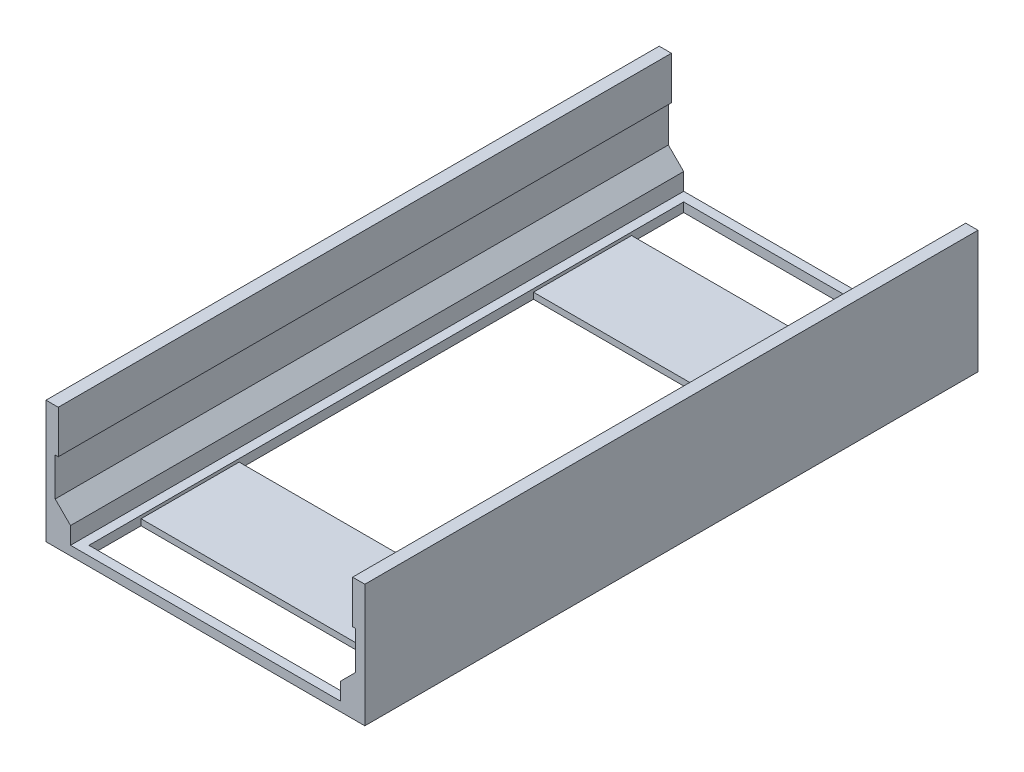
SolidWorks part; units mm, degrees
ref_plane "Plano frontal" through (0, 0, 0) normal (0, 0, 1) x (1, 0, 0)
ref_plane "Plano superior" through (0, 0, 0) normal (0, 1, 0) x (1, 0, 0)
ref_plane "Plano direito" through (0, 0, 0) normal (1, 0, 0) x (0, 0, -1)
sketch "Esboço1" plane through (0, 0, 0) normal (0, 0, 1) x (1, 0, 0)
  line L0 (-24, 14) -> (-24, -14) construction
  line L1 (24, 14) -> (24, -14) construction
  line L2 (-22.5, 12.5) -> (-22.5, -7.5)
  line L3 (-17.5, -12.5) -> (17.5, -12.5)
  line L4 (22.5, 12.5) -> (22.5, -7.5)
  line L5 (-22.5, 12.5) -> (22.5, -12.5) construction
  line L6 (-22.5, -12.5) -> (22.5, 12.5) construction
  line L7 (24, 12.5) -> (24, -9)
  line L8 (-19, -14) -> (19, -14)
  line L9 (-24, 12.5) -> (-24, -9)
  line L10 (-22.5, 12.5) -> (-24, 12.5)
  line L11 (22.5, 12.5) -> (24, 12.5)
  line L12 (-22.5, -12.5) -> (22.5, -12.5) construction
  line L13 (-22.5, 12.5) -> (22.5, 12.5) construction
  line L14 (-24, 14) -> (24, 14) construction
  line L15 (22.5, 12.5) -> (22.5, -12.5) construction
  line L16 (17.5, -12.5) -> (22.5, -7.5)
  line L17 (-24, -14) -> (24, -14) construction
  line L18 (24, -9) -> (19, -14)
  line L19 (-22.5, 12.5) -> (-22.5, -12.5) construction
  line L20 (-22.5, -7.5) -> (-17.5, -12.5)
  line L21 (-24, -9) -> (-19, -14)
  point P0 (0, 0)
  dimension "D1" = 25
  dimension "D2" = 45
  dimension "D3" = 1.5
extrude "Ressalto-extrusão1" add sketch "Esboço1" along normal blind 100
sketch "Esboço3" plane through (0, -12.5, 0) normal (0, 1, 0) x (1, 0, 0)
  line L0 (22.5, -100) -> (22.5, 0) construction
  line L1 (-22.5, 0) -> (22.5, 0)
  line L2 (-22.5, 0) -> (-22.5, -1.5)
  line L3 (-22.5, -1.5) -> (22.5, -1.5)
  line L4 (22.5, 0) -> (22.5, -1.5)
  dimension "D1" = 1.5
extrude "Ressalto-extrusão3" add sketch "Esboço3" along normal up to surface (25 mm away) up to face at (-23.25, 12.5, 50)
sketch "Esboço4" plane through (0, 0, 1.5) normal (0, 0, 1) x (1, 0, 0)
  line L0 (17.5, -12.5) -> (-17.5, -12.5) construction
  line L1 (-10, -12.5) -> (10, -12.5)
  line L2 (-10, -12.5) -> (-10, -7.5)
  line L3 (-5, -2.5) -> (5, -2.5)
  line L4 (10, -12.5) -> (10, -7.5)
  line L5 (-10, -7.5) -> (-5, -2.5)
  line L6 (5, -2.5) -> (10, -7.5)
  point P1 (10, -2.5)
  point P2 (-10, -2.5)
  point P4 (0, -12.5)
  point P5 (0, -12.5)
extrude "Corte-extrusão1" cut sketch "Esboço4" against normal through all
sketch "Esboço5" plane through (0, -12.5, 0) normal (0, 1, 0) x (1, 0, 0)
  line L0 (0, 0) -> (0, -2.25) construction
  line L1 (22.5, -1.5) -> (-22.5, -1.5) construction
  line L2 (-6, -3) -> (6, -3)
  line L3 (-6, -3) -> (-6, -1.5)
  line L4 (-6, -1.5) -> (6, -1.5)
  line L5 (6, -3) -> (6, -1.5)
  line L6 (-6, -3) -> (6, -1.5) construction
  line L7 (-6, -1.5) -> (6, -3) construction
  dimension "D1" = 2.25
  dimension "D2" = 12
extrude "Corte-extrusão2" cut sketch "Esboço5" against normal through all
sketch "Esboço6" plane through (0, -12.5, 0) normal (0, 1, 0) x (1, 0, 0)
  line L0 (22.5, -100) -> (22.5, -1.5) construction
  line L1 (-22.5, -100) -> (22.5, -100)
  line L2 (-22.5, -100) -> (-22.5, -98)
  line L3 (-22.5, -98) -> (22.5, -98)
  line L4 (22.5, -100) -> (22.5, -98)
extrude "Ressalto-extrusão4" add sketch "Esboço6" along normal up to surface (25 mm away) up to face at (0, 12.5, 50.375)
sketch "Esboço7" plane through (0, 0, 100) normal (0, 0, 1) x (1, 0, 0)
  line L0 (0, 12.5) -> (0, 8.5) construction
  line L1 (24, 12.5) -> (-24, 12.5) construction
  line L2 (0, 8.5) -> (1, 8.5) construction
  line L3 (1, 8.5) -> (0, 8.5) construction
  line L4 (0, 8.5) -> (0, 0.5) construction
  line L5 (0, 0.5) -> (1, 0.5) construction
  line L6 (1, 0.5) -> (0, 0.5) construction
  line L7 (0, 0.5) -> (0, -7.5) construction
  line L8 (0, 8.5) -> (-8, 8.5) construction
  line L9 (-8, 8.5) -> (-16, 8.5) construction
  line L10 (-9.4, 9.9) -> (-6.6, 9.9)
  line L11 (-17.4, 9.9) -> (-14.6, 9.9)
  line L12 (-17.4, 9.9) -> (-17.4, 7.1)
  line L13 (-17.4, 7.1) -> (-14.6, 7.1)
  line L14 (-14.6, 9.9) -> (-14.6, 7.1)
  line L15 (-17.4, 9.9) -> (-14.6, 7.1) construction
  line L16 (-17.4, 7.1) -> (-14.6, 9.9) construction
  line L17 (-9.4, 9.9) -> (-9.4, 7.1)
  line L18 (-9.4, 7.1) -> (-6.6, 7.1)
  line L19 (-6.6, 9.9) -> (-6.6, 7.1)
  line L20 (-9.4, 9.9) -> (-6.6, 7.1) construction
  line L21 (-9.4, 7.1) -> (-6.6, 9.9) construction
  line L22 (-1.4, 9.9) -> (1.4, 9.9)
  line L23 (-1.4, 9.9) -> (-1.4, 7.1)
  line L24 (-1.4, 7.1) -> (1.4, 7.1)
  line L25 (1.4, 9.9) -> (1.4, 7.1)
  line L26 (-1.4, 9.9) -> (1.4, 7.1) construction
  line L27 (-1.4, 7.1) -> (1.4, 9.9) construction
  line L28 (6.6, 9.9) -> (9.4, 9.9)
  line L29 (6.6, 9.9) -> (6.6, 7.1)
  line L30 (6.6, 7.1) -> (9.4, 7.1)
  line L31 (9.4, 9.9) -> (9.4, 7.1)
  line L32 (6.6, 9.9) -> (9.4, 7.1) construction
  line L33 (6.6, 7.1) -> (9.4, 9.9) construction
  line L34 (14.6, 9.9) -> (17.4, 9.9)
  line L35 (14.6, 9.9) -> (14.6, 7.1)
  line L36 (14.6, 7.1) -> (17.4, 7.1)
  line L37 (17.4, 9.9) -> (17.4, 7.1)
  line L38 (14.6, 9.9) -> (17.4, 7.1) construction
  line L39 (14.6, 7.1) -> (17.4, 9.9) construction
  line L40 (-9.4, 1.9) -> (-6.6, 1.9)
  line L41 (-9.4, 1.9) -> (-9.4, -0.9)
  line L42 (-9.4, -0.9) -> (-6.6, -0.9)
  line L43 (-6.6, 1.9) -> (-6.6, -0.9)
  line L44 (-9.4, 1.9) -> (-6.6, -0.9) construction
  line L45 (-9.4, -0.9) -> (-6.6, 1.9) construction
  line L46 (-1.4, 1.9) -> (1.4, 1.9)
  line L47 (-1.4, 1.9) -> (-1.4, -0.9)
  line L48 (-1.4, -0.9) -> (1.4, -0.9)
  line L49 (1.4, 1.9) -> (1.4, -0.9)
  line L50 (-1.4, 1.9) -> (1.4, -0.9) construction
  line L51 (-1.4, -0.9) -> (1.4, 1.9) construction
  line L52 (6.6, 1.9) -> (9.4, 1.9)
  line L53 (6.6, 1.9) -> (6.6, -0.9)
  line L54 (6.6, -0.9) -> (9.4, -0.9)
  line L55 (9.4, 1.9) -> (9.4, -0.9)
  line L56 (6.6, 1.9) -> (9.4, -0.9) construction
  line L57 (6.6, -0.9) -> (9.4, 1.9) construction
  line L58 (14.6, 1.9) -> (17.4, 1.9)
  line L59 (14.6, 1.9) -> (14.6, -0.9)
  line L60 (14.6, -0.9) -> (17.4, -0.9)
  line L61 (17.4, 1.9) -> (17.4, -0.9)
  line L62 (14.6, 1.9) -> (17.4, -0.9) construction
  line L63 (14.6, -0.9) -> (17.4, 1.9) construction
  line L64 (-9.4, -6.1) -> (-6.6, -6.1)
  line L65 (-9.4, -6.1) -> (-9.4, -8.9)
  line L66 (-9.4, -8.9) -> (-6.6, -8.9)
  line L67 (-6.6, -6.1) -> (-6.6, -8.9)
  line L68 (-9.4, -6.1) -> (-6.6, -8.9) construction
  line L69 (-9.4, -8.9) -> (-6.6, -6.1) construction
  line L70 (-1.4, -6.1) -> (1.4, -6.1)
  line L71 (-1.4, -6.1) -> (-1.4, -8.9)
  line L72 (-1.4, -8.9) -> (1.4, -8.9)
  line L73 (1.4, -6.1) -> (1.4, -8.9)
  line L74 (-1.4, -6.1) -> (1.4, -8.9) construction
  line L75 (-1.4, -8.9) -> (1.4, -6.1) construction
  line L76 (6.6, -6.1) -> (9.4, -6.1)
  line L77 (6.6, -6.1) -> (6.6, -8.9)
  line L78 (6.6, -8.9) -> (9.4, -8.9)
  line L79 (9.4, -6.1) -> (9.4, -8.9)
  line L80 (6.6, -6.1) -> (9.4, -8.9) construction
  line L81 (6.6, -8.9) -> (9.4, -6.1) construction
  line L82 (14.6, -6.1) -> (17.4, -6.1)
  line L83 (14.6, -6.1) -> (14.6, -8.9)
  line L84 (14.6, -8.9) -> (17.4, -8.9)
  line L85 (17.4, -6.1) -> (17.4, -8.9)
  line L86 (14.6, -6.1) -> (17.4, -8.9) construction
  line L87 (14.6, -8.9) -> (17.4, -6.1) construction
  line L88 (-17.4, 1.9) -> (-14.6, 1.9)
  line L89 (-17.4, 1.9) -> (-17.4, -0.9)
  line L90 (-17.4, -0.9) -> (-14.6, -0.9)
  line L91 (-14.6, 1.9) -> (-14.6, -0.9)
  line L92 (-17.4, 1.9) -> (-14.6, -0.9) construction
  line L93 (-17.4, -0.9) -> (-14.6, 1.9) construction
  line L94 (-17.4, -6.1) -> (-14.6, -6.1)
  line L95 (-17.4, -6.1) -> (-17.4, -8.9)
  line L96 (-17.4, -8.9) -> (-14.6, -8.9)
  line L97 (-14.6, -6.1) -> (-14.6, -8.9)
  line L98 (-17.4, -6.1) -> (-14.6, -8.9) construction
  line L99 (-17.4, -8.9) -> (-14.6, -6.1) construction
  dimension "D1" = 2.8
  dimension "D2" = 5
  dimension "D3" = 3
extrude "Corte-extrusão3" cut sketch "Esboço7" against normal blind 10
sketch "Esboço8" plane through (0, 0, 0) normal (0, 0, -1) x (-1, 0, 0)
  line L3 (-22.5, -10.5) -> (-22.5, -12.5)
  line L4 (-20.5, -12.5) -> (-22.5, -10.5)
  line L5 (-22.5, -12.5) -> (-20.5, -12.5)
  line L6 (-22.5, -10.5) -> (-22.5, -12.5)
  line L7 (-20.5, -12.5) -> (-22.5, -10.5)
  line L8 (-22.5, -12.5) -> (-20.5, -12.5)
  line L9 (20.5, -12.5) -> (22.5, -12.5)
  line L10 (22.5, -10.5) -> (20.5, -12.5)
  line L11 (22.5, -12.5) -> (22.5, -10.5)
  line L12 (20.5, -12.5) -> (22.5, -12.5)
  line L13 (22.5, -10.5) -> (20.5, -12.5)
  line L14 (22.5, -12.5) -> (22.5, -10.5)
  dimension "D1" = 0
  dimension "D2" = 0
extrude "Corte-extrusão4" cut sketch "Esboço8" against normal through all
sketch "Esboço9" plane through (0, 0, 0) normal (0, 0, -1) x (-1, 0, 0)
  line L0 (-19, -14) -> (-21.5, -14)
  line L1 (-21.5, -14) -> (-21.5, -11.5)
  line L2 (-19, -14) -> (-24, -9) construction
  line L3 (-21.5, -11.5) -> (-19, -14)
  line L4 (19, -14) -> (21.5, -14)
  line L5 (21.5, -14) -> (21.5, -11.5)
  line L6 (24, -9) -> (19, -14) construction
  line L7 (21.5, -11.5) -> (19, -14)
extrude "Ressalto-extrusão5" add sketch "Esboço9" against normal through all
sketch "Esboço10" plane through (0, 0, 0) normal (0, 0, -1) x (-1, 0, 0)
  line L0 (0, 0) -> (0, 16.2548) construction
  line L1 (-24, 12.5) -> (-24, 4.5) construction
  line L2 (-24, -9) -> (-24, 12.5) construction
  line L3 (-24, 4.5) -> (-23.5, 4.5)
  line L4 (-23.5, 4.5) -> (-23.5, -3.5)
  line L5 (-23.5, -3.5) -> (-24, -3.5)
  line L6 (-24, -3.5) -> (-24, 4.5)
  line L7 (24, -3.5) -> (24, 4.5)
  line L8 (23.5, -3.5) -> (24, -3.5)
  line L9 (23.5, 4.5) -> (23.5, -3.5)
  line L10 (24, 4.5) -> (23.5, 4.5)
extrude "Corte-extrusão5" cut sketch "Esboço10" against normal through all
chamfer "Chanfro1" distance 3 angle 45 5 edges at (-22.5, 2.5, 98) (-20, -10, 98) (22.5, 2.5, 98) (20, -10, 98) (0, -12.5, 98)
chamfer "Chanfro2" distance 3 angle 45 6 edges at (-22.5, 2.5, 1.5) (-20, -10, 1.5) (-13.75, -12.5, 1.5) (13.75, -12.5, 1.5) (20, -10, 1.5) (22.5, 2.5, 1.5)
sketch "Esboço11" plane through (0, 0, 0) normal (0, 0, -1) x (-1, 0, 0)
  line L0 (24.5, -9.2071) -> (24.5, -3)
  line L1 (24.5, -3) -> (24, -3)
  line L2 (24, -3) -> (24, 4)
  line L3 (24, 4) -> (26, 4)
  line L4 (26, 4) -> (26, -14.5)
  line L5 (26, -14.5) -> (26, -16)
  line L6 (26, -16) -> (-26, -16)
  line L7 (0, -16) -> (0, 0) construction
  line L8 (-24, 4) -> (-24, -3)
  line L9 (-24, -3) -> (-24.5, -3)
  line L10 (-24.5, -3) -> (-24.5, -9.2071)
  line L11 (-24.5, -9.2071) -> (-22, -11.7071)
  line L12 (-22, -11.7071) -> (-22, -14.5)
  line L13 (-22, -14.5) -> (22, -14.5)
  line L14 (22, -14.5) -> (22, -11.7071)
  line L15 (22, -11.7071) -> (24.5, -9.2071)
  line L16 (24, -9) -> (24, -3.5)
  line L17 (24, -3.5) -> (23.5, -3.5)
  line L18 (23.5, -3.5) -> (23.5, 4.5)
  line L19 (23.5, 4.5) -> (24, 4.5)
  line L20 (24, 4.5) -> (24, 12.5)
  line L21 (24, 12.5) -> (-24, 12.5)
  line L22 (-24, 12.5) -> (-24, 4.5)
  line L23 (-24, 4.5) -> (-23.5, 4.5)
  line L24 (-23.5, 4.5) -> (-23.5, -3.5)
  line L25 (-23.5, -3.5) -> (-24, -3.5)
  line L26 (-24, -3.5) -> (-24, -9)
  line L27 (-24, -9) -> (-21.5, -11.5)
  line L28 (-21.5, -11.5) -> (-21.5, -14)
  line L29 (-21.5, -14) -> (21.5, -14)
  line L30 (21.5, -14) -> (21.5, -11.5)
  line L31 (21.5, -11.5) -> (24, -9)
  line L32 (24, -9) -> (24, -3.5) construction
  line L33 (24, -3.5) -> (23.5, -3.5) construction
  line L34 (23.5, -3.5) -> (23.5, 4.5) construction
  line L35 (23.5, 4.5) -> (24, 4.5) construction
  line L36 (24, 4.5) -> (24, 12.5) construction
  line L37 (24, 12.5) -> (-24, 12.5) construction
  line L38 (-24, 12.5) -> (-24, 4.5) construction
  line L39 (-24, 4.5) -> (-23.5, 4.5) construction
  line L40 (-23.5, 4.5) -> (-23.5, -3.5) construction
  line L41 (-23.5, -3.5) -> (-24, -3.5) construction
  line L42 (-24, -3.5) -> (-24, -9) construction
  line L43 (-24, -9) -> (-21.5, -11.5) construction
  line L44 (-21.5, -11.5) -> (-21.5, -14) construction
  line L45 (-21.5, -14) -> (21.5, -14) construction
  line L46 (21.5, -14) -> (21.5, -11.5) construction
  line L47 (21.5, -11.5) -> (24, -9) construction
  line L48 (24, 4) -> (24.5, 4) construction
  line L49 (24.5, 4) -> (24.5, 13) construction
  line L50 (-24.5, 4) -> (-24, 4) construction
  line L51 (-24.5, 13) -> (-24.5, 4) construction
  line L52 (24.5, 13) -> (-24.5, 13) construction
  line L53 (-26, -14.5) -> (-26, -16)
  line L54 (-26, 4) -> (-26, -14.5)
  line L55 (-24, 4) -> (-26, 4)
  dimension "D3" = 18.5
  dimension "D1" = 0
  dimension "D2" = 0.5
extrude "Ressalto-extrusão6" add sketch "Esboço11" against normal through all separate body
sketch "Esboço12" plane through (0, 0, 0) normal (0, 0, -1) x (-1, 0, 0)
  line L16 (24, -9) -> (24, -3.5)
  line L17 (24, -3.5) -> (23.5, -3.5)
  line L18 (23.5, -3.5) -> (23.5, 4.5)
  line L19 (23.5, 4.5) -> (24, 4.5)
  line L20 (24, 4.5) -> (24, 12.5)
  line L21 (24, 12.5) -> (-24, 12.5)
  line L22 (-24, 12.5) -> (-24, 4.5)
  line L23 (-24, 4.5) -> (-23.5, 4.5)
  line L24 (-23.5, 4.5) -> (-23.5, -3.5)
  line L25 (-23.5, -3.5) -> (-24, -3.5)
  line L26 (-24, -3.5) -> (-24, -9)
  line L27 (-24, -9) -> (-21.5, -11.5)
  line L28 (-21.5, -11.5) -> (-21.5, -14)
  line L29 (-21.5, -14) -> (21.5, -14)
  line L30 (21.5, -14) -> (21.5, -11.5)
  line L31 (21.5, -11.5) -> (24, -9)
  line L32 (24, -9) -> (24, -3.5)
  line L33 (24, -3.5) -> (23.5, -3.5)
  line L34 (23.5, -3.5) -> (23.5, 4.5)
  line L35 (23.5, 4.5) -> (24, 4.5)
  line L36 (24, 4.5) -> (24, 12.5)
  line L37 (24, 12.5) -> (-24, 12.5)
  line L38 (-24, 12.5) -> (-24, 4.5)
  line L39 (-24, 4.5) -> (-23.5, 4.5)
  line L40 (-23.5, 4.5) -> (-23.5, -3.5)
  line L41 (-23.5, -3.5) -> (-24, -3.5)
  line L42 (-24, -3.5) -> (-24, -9)
  line L43 (-24, -9) -> (-21.5, -11.5)
  line L44 (-21.5, -11.5) -> (-21.5, -14)
  line L45 (-21.5, -14) -> (21.5, -14)
  line L46 (21.5, -14) -> (21.5, -11.5)
  line L47 (21.5, -11.5) -> (24, -9)
  dimension "D1" = 0
extrude "Corte-extrusão6" cut sketch "Esboço12" against normal through all
sketch "Esboço13" plane through (0, -14.5, 0) normal (0, 1, 0) x (1, 0, 0)
  line L0 (20.5, -1.5) -> (-20.5, -1.5)
  line L1 (-20.5, -1.5) -> (-20.5, -98.5001)
  line L2 (-20.5, -98.5001) -> (20.5, -98.5001)
  line L3 (20.5, -98.5001) -> (20.5, -1.5)
  line L4 (22, 0) -> (-22, 0)
  line L5 (-22, 0) -> (-22, -100.0001)
  line L6 (-22, -100.0001) -> (22, -100.0001)
  line L7 (22, -100.0001) -> (22, 0)
  line L8 (22, 0) -> (-22, 0) construction
  line L9 (-22, 0) -> (-22, -100.0001) construction
  line L10 (-22, -100.0001) -> (22, -100.0001) construction
  line L11 (22, -100.0001) -> (22, 0) construction
  dimension "D1" = 0
  dimension "D2" = 1.5
extrude "Corte-extrusão7" cut sketch "Esboço13" against normal through all
sketch "Esboço14" plane through (0, -16, 0) normal (0, -1, 0) x (1, 0, 0)
  line L0 (-20.5, 50) -> (20.5, 50) construction
  line L1 (-20.5, 1.5) -> (-20.5, 98.5001) construction
  line L2 (20.5, 98.5001) -> (20.5, 1.5) construction
  line L3 (-20.5, 98.5001) -> (-20.5, 90.0001) construction
  line L4 (-20.5, 90.0001) -> (20.5, 90.0001)
  line L5 (20.5, 90.0001) -> (20.5, 74.0001)
  line L6 (20.5, 74.0001) -> (-20.5, 74.0001)
  line L7 (-20.5, 74.0001) -> (-20.5, 90.0001)
  line L8 (-20.5, 26) -> (-20.5, 10)
  line L9 (20.5, 26) -> (-20.5, 26)
  line L10 (20.5, 10) -> (20.5, 26)
  line L11 (-20.5, 10) -> (20.5, 10)
extrude "Ressalto-extrusão7" add sketch "Esboço14" against normal blind 1
